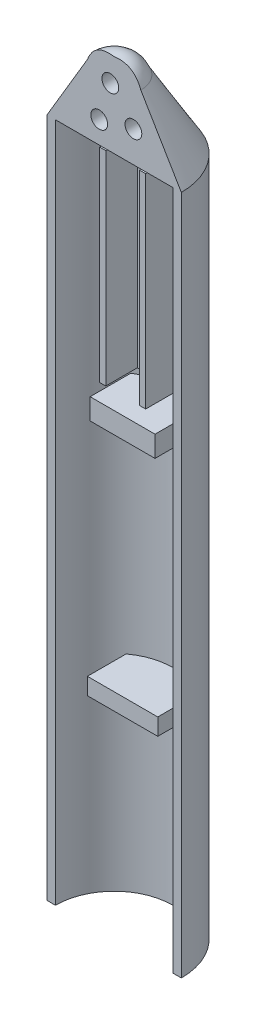
SolidWorks part; units mm, degrees
ref_plane "Front Plane" through (0, 0, 0) normal (0, 0, 1) x (1, 0, 0)
ref_plane "Top Plane" through (0, 0, 0) normal (0, 1, 0) x (1, 0, 0)
ref_plane "Right Plane" through (0, 0, 0) normal (1, 0, 0) x (0, 0, -1)
sketch "Sketch1" plane through (0, 0, 0) normal (0, 0, 1) x (1, 0, 0)
  line L0 (0, 91) -> (0, -91) construction
  line L1 (6.354, 87.279) -> (16, 71)
  line L2 (16, 71) -> (0, 71)
  line L3 (0, 91) -> (0, 71)
  spline S0 degree 2 poles (0, 91) (4.6686, 91.7236) (6.354, 87.279) knots 0 0 0 1 1 1
  point P3 (0, 0)
  dimension "D1" = 182
  dimension "D2" = 16
  dimension "D3" = 91
  dimension "D4" = 20
revolve "Revolve1" add sketch "Sketch1" angle 360 about L0
sketch "Sketch2" plane through (0, 0, 0) normal (0, 0, 1) x (1, 0, 0)
  line L0 (16, 71) -> (16, -91.0399)
  line L1 (16, -91.0399) -> (14, -91.0399)
  line L2 (14, -91.0399) -> (14, 71)
  line L3 (16, 71) -> (0, 71) construction
  line L4 (14, 71) -> (16, 71)
  dimension "D1" = 2
revolve "Revolve2" add sketch "Sketch2" angle 360 about L0
sketch "Sketch5" plane through (0, 0, 0) normal (0, 0, 1) x (1, 0, 0)
  line L1 (36.3918, -96.4232) -> (-36.3918, -96.4232)
  line L2 (36.3918, -96.4232) -> (36.3918, 96.4232)
  line L3 (36.3918, 96.4232) -> (-36.3918, 96.4232)
  line L4 (-36.3918, -96.4232) -> (-36.3918, 96.4232)
  line L5 (36.3918, -96.4232) -> (-36.3918, 96.4232) construction
  line L6 (36.3918, 96.4232) -> (-36.3918, -96.4232) construction
  point P0 (0, 0)
extrude "Cut-Extrude1" cut sketch "Sketch5" along normal through all
sketch "Sketch4" plane through (0, 0, 0) normal (0, 0, 1) x (1, 0, 0)
  line L0 (0, 91) -> (0, -91) construction
  line L5 (9, 7) -> (-9, 7)
  line L6 (9, 7) -> (9, -38)
  line L7 (9, -38) -> (-9, -38)
  line L8 (-9, 7) -> (-9, -38)
  line L9 (9, 7) -> (-9, -38) construction
  line L10 (9, -38) -> (-9, 7) construction
  line L11 (0, -100.299) -> (0, 100.299) construction
  line L12 (-7.7289, 11) -> (7.7289, 11)
  line L13 (-7.7289, 11) -> (-7.7289, 16)
  line L14 (-7.7289, 16) -> (7.7289, 16)
  line L15 (7.7289, 11) -> (7.7289, 16)
  line L16 (-7.7289, 11) -> (7.7289, 16) construction
  line L17 (-7.7289, 16) -> (7.7289, 11) construction
  line L18 (-8.3816, -46) -> (8.3816, -46)
  line L19 (-8.3816, -46) -> (-8.3816, -42)
  line L20 (-8.3816, -42) -> (8.3816, -42)
  line L21 (8.3816, -46) -> (8.3816, -42)
  line L22 (-8.3816, -46) -> (8.3816, -42) construction
  line L23 (-8.3816, -42) -> (8.3816, -46) construction
  line L24 (5.5, 20.0676) -> (4, 20.0676)
  line L25 (5.5, 20.0676) -> (5.5, 68.622)
  line L26 (5.5, 68.622) -> (4, 68.622)
  line L27 (4, 20.0676) -> (4, 68.622)
  line L28 (5.5, 20.0676) -> (4, 68.622) construction
  line L29 (5.5, 68.622) -> (4, 20.0676) construction
  line L30 (-5.5, 68.622) -> (-4, 20.0676) construction
  line L31 (-5.5, 20.0676) -> (-4, 68.622) construction
  line L32 (-4, 20.0676) -> (-4, 68.622)
  line L33 (-5.5, 68.622) -> (-4, 68.622)
  line L34 (-5.5, 20.0676) -> (-5.5, 68.622)
  line L35 (-5.5, 20.0676) -> (-4, 20.0676)
  line L36 (-4, 68.622) -> (4, 68.622)
  line L37 (-4, 20.0676) -> (4, 20.0676)
  point P0 (0, -15.5)
  point P1 (0, 13.5)
  point P12 (0, -44)
  point P17 (0, 16)
  point P19 (4.75, 44.3448)
  point P30 (-4.75, 44.3448)
  point P31 (0, 0)
  point P32 (0, -17.7803)
  point P33 (0, -44.9352)
  dimension "D1" = 45
  dimension "D2" = 18
  dimension "D3" = 55
  dimension "D4" = 1.5
  dimension "D5" = 4
  dimension "D6" = 5
  dimension "D7" = 4
  dimension "D8" = 4
  dimension "D9" = 4
extrude "Boss-Extrude1" add sketch "Sketch4" against normal up to next from offset 2 contours L12 L15 L14 L13 | L18 L21 L20 L19 | L27 L24 L25 L26 | L34 L35 L32 L33 region at (0, 13.5, 0) region at (0, -44, 0) region at (4.75, 44.3448, 0) region at (-4.75, 44.3448, 0) offset against normal yes
extrude "Boss-Extrude2" add sketch "Sketch4<4>" against normal up to next from offset 9.5 contours L32 L37 L27 L36 region at (0, 44.3448, 0) offset against normal yes
sketch "Sketch4<4>" plane through (0, 0, 0) normal (0, 0, 1) x (1, 0, 0) same geometry as "Sketch4"
sketch "Sketch6" plane through (0, 0, 0) normal (0, 0, 1) x (1, 0, 0)
  circle A0 centre (4.5793, 78.3675) radius 2
  circle A1 centre (-3.5585, 76.2554) radius 2
  circle A2 centre (-0.9193, 85.0766) radius 2
  dimension "D1" = 4
  dimension "D2" = 4
  dimension "D3" = 4
extrude "Cut-Extrude2" cut sketch "Sketch6" against normal blind 4
